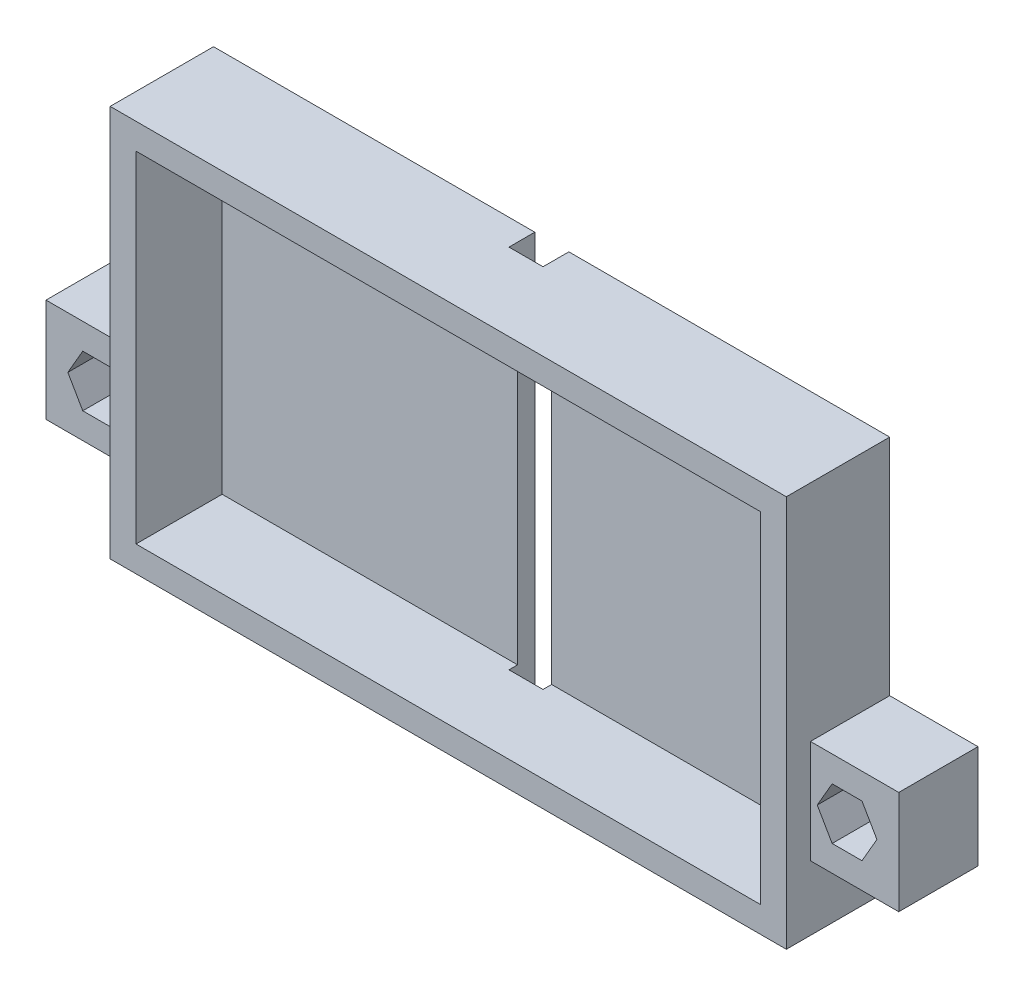
SolidWorks part; units mm, degrees
ref_plane "Plano frontal" through (0, 0, 0) normal (0, 0, 1) x (1, 0, 0)
ref_plane "Plano superior" through (0, 0, 0) normal (0, 1, 0) x (1, 0, 0)
ref_plane "Plano direito" through (0, 0, 0) normal (1, 0, 0) x (0, 0, -1)
sketch "Esboço1" plane through (0, 0, 0) normal (0, 0, 1) x (1, 0, 0)
  line L0 (0, 0) -> (0, 10.5) construction
  line L1 (0, 0) -> (-72.5, 0)
  line L2 (0, 0) -> (0, 39.5)
  line L3 (0, 39.5) -> (-72.5, 39.5)
  line L4 (-72.5, 0) -> (-72.5, 39.5)
  line L5 (-72.5, 0) -> (-72.5, 10.5) construction
  line L6 (0, 10.5) -> (7.25, 10.5) construction
  line L7 (-72.5, 10.5) -> (-79.75, 10.5) construction
  line L8 (-72.5, 39.5) -> (-75.5, 39.5) construction
  line L9 (-72.5, 39.5) -> (-72.5, 42.5) construction
  line L10 (0, 0) -> (3, 0) construction
  line L11 (0, 0) -> (0, -3) construction
  line L12 (-79.75, 10.5) -> (-79.75, 16.5) construction
  line L13 (-75.5, 42.5) -> (3, 42.5)
  line L14 (-75.5, 42.5) -> (-75.5, -3)
  line L15 (-75.5, -3) -> (3, -3)
  line L16 (3, 42.5) -> (3, -3)
  line L17 (-79.75, 10.5) -> (-85.75, 10.5) construction
  line L18 (-79.75, 10.5) -> (-79.75, 4.5) construction
  line L19 (7.25, 10.5) -> (7.25, 16.5) construction
  line L20 (7.25, 10.5) -> (13.25, 10.5) construction
  line L21 (7.25, 10.5) -> (7.25, 4.5) construction
  line L23 (-85.75, 16.5) -> (-75.5, 16.5)
  line L24 (-85.75, 16.5) -> (-85.75, 4.5)
  line L25 (-85.75, 4.5) -> (-75.5, 4.5)
  line L26 (-75.5, 16.5) -> (-75.5, 4.5)
  line L27 (13.25, 4.5) -> (3, 4.5)
  line L28 (13.25, 4.5) -> (13.25, 16.5)
  line L29 (13.25, 16.5) -> (3, 16.5)
  line L30 (3, 4.5) -> (3, 16.5)
  circle A0 centre (-79.75, 10.5) radius 1.6
  circle A1 centre (7.25, 10.5) radius 1.6
extrude "Ressalto-extrusão1" add sketch "Esboço1" along normal blind 2 contours L4 L3 L2 L1
extrude "Ressalto-extrusão2" add sketch "Esboço1<3>" along normal blind 12 contours L16 L13 L14 L15 L1 L4 L3 L2 region at (-36.25, 41.5927, 0)
sketch "Esboço1<3>" plane through (0, 0, 0) normal (0, 0, 1) x (1, 0, 0) same geometry as "Esboço1"
extrude "Ressalto-extrusão3" add sketch "Esboço1<4>" along normal blind 6 contours L24 L25 L14 L23 A0 | L28 L29 L16 L27 A1 region at (-75.6578, 10.5, 0) region at (8.125, 16.3422, 0)
sketch "Esboço1<4>" plane through (0, 0, 0) normal (0, 0, 1) x (1, 0, 0) same geometry as "Esboço1"
sketch "Esboço3" plane through (0, 0, 0) normal (0, 0, -1) x (-1, 0, 0)
  line L0 (79.75, 10.5) -> (79.75, 22.5) construction
  line L1 (79.75, 22.5) -> (68.25, 22.5) construction
  line L2 (75.5, -3) -> (-3, -3) construction
  line L3 (68.25, 22.5) -> (58.55, 22.5)
  line L4 (68.25, 22.5) -> (68.25, 25.7)
  line L5 (68.25, 25.7) -> (58.55, 25.7)
  line L6 (58.55, 22.5) -> (58.55, 25.7)
  line L7 (36.25, -3) -> (36.25, 42.5) construction
  line L8 (75.5, 42.5) -> (-3, 42.5) construction
  line L9 (-7.25, 10.5) -> (-7.25, 22.5) construction
  line L10 (-7.25, 22.5) -> (4.25, 22.5) construction
  line L11 (13.95, 22.5) -> (13.95, 25.7)
  line L12 (4.25, 25.7) -> (13.95, 25.7)
  line L13 (4.25, 22.5) -> (4.25, 25.7)
  line L14 (4.25, 22.5) -> (13.95, 22.5)
  line L15 (36.25, -3) -> (34.25, -3) construction
extrude "Ressalto-extrusão4" add sketch "Esboço3" along normal blind 3.5
sketch "Esboço5" plane through (0, 0, 0) normal (0, 0, -1) x (-1, 0, 0)
  line L0 (36.25, -3) -> (36.25, 42.5) construction
  line L1 (75.5, -3) -> (-3, -3) construction
  line L2 (75.5, 42.5) -> (-3, 42.5) construction
  line L3 (36.25, -3) -> (34.25, -3) construction
  line L5 (34.25, -3) -> (38.2025, -3)
  line L6 (34.25, -3) -> (34.25, 42.5)
  line L7 (34.25, 42.5) -> (38.2025, 42.5)
  line L8 (38.2025, -3) -> (38.2025, 42.5)
extrude "Corte-extrusão4" cut sketch "Esboço5" against normal blind 3
sketch "Esboço7" plane through (-58.55, 0, 0) normal (1, 0, 0) x (0, 0, -1)
  line L0 (3.5, 25.7) -> (3.5, 26.2)
  line L1 (3.5, 25.7) -> (4.5, 25.7) construction
  line L2 (3.5, 26.2) -> (4.5, 25.7)
  line L3 (4.5, 25.7) -> (3.5, 22.5)
  line L10 (3.5, 22.5) -> (3.5, 25.7)
extrude "Ressalto-extrusão5" add sketch "Esboço7" against normal up to surface (9.7 mm away) up to face at (-68.25, 24.1, -1.75)
sketch "Esboço8" plane through (-4.25, 0, 0) normal (1, 0, 0) x (0, 0, -1)
  line L0 (3.5, 25.7) -> (3.5, 26.2)
  line L1 (3.5, 25.7) -> (4.5, 25.7) construction
  line L2 (3.5, 26.2) -> (4.5, 25.7)
  line L3 (4.5, 25.7) -> (3.5, 22.5)
  line L15 (3.5, 22.5) -> (3.5, 25.7)
extrude "Ressalto-extrusão6" add sketch "Esboço8" against normal up to surface (9.7 mm away) up to face at (-13.95, 24.1, -1.75)
ref_plane "Plano1" through (0, 0, -10) normal (0, 0, -1) x (-1, 0, 0)
sketch "Esboço9" plane through (0, 0, -10) normal (0, 0, -1) x (-1, 0, 0)
  line L1 (-2.547, 31.4646) -> (77.239, 31.4646)
  line L2 (-2.547, 31.4646) -> (-2.547, 10.2704)
  line L3 (-2.547, 10.2704) -> (77.239, 10.2704)
  line L4 (77.239, 31.4646) -> (77.239, 10.2704)
extrude "Corte-extrusão5" cut sketch "Esboço9" against normal up to vertex (10 mm away) up to point (3, 42.5, 0)
sketch "Esboço10" plane through (0, 0, 6) normal (0, 0, 1) x (1, 0, 0)
  line L0 (-85.75, 16.5) -> (-85.75, 4.5) construction
  line L1 (-85.75, 4.5) -> (-75.5, 4.5) construction
  line L2 (-75.5, 4.5) -> (-75.5, 16.5) construction
  line L3 (-75.5, 16.5) -> (-85.75, 16.5) construction
  line L4 (13.25, 4.5) -> (13.25, 16.5) construction
  line L5 (13.25, 16.5) -> (3, 16.5) construction
  line L6 (3, 16.5) -> (3, 4.5) construction
  line L7 (3, 4.5) -> (13.25, 4.5) construction
  line L8 (-85.75, 16.5) -> (-85.75, 4.5)
  line L9 (-85.75, 4.5) -> (-75.5, 4.5)
  line L10 (-75.5, 4.5) -> (-75.5, 16.5)
  line L11 (-75.5, 16.5) -> (-85.75, 16.5)
  line L12 (13.25, 4.5) -> (13.25, 16.5)
  line L13 (13.25, 16.5) -> (3, 16.5)
  line L14 (3, 16.5) -> (3, 4.5)
  line L15 (3, 4.5) -> (13.25, 4.5)
sketch "Esboço11" plane through (0, 0, 6) normal (0, 0, 1) x (1, 0, 0)
  line L0 (13.25, 4.5) -> (13.25, 16.5) construction
  line L1 (13.25, 16.5) -> (3, 16.5) construction
  line L2 (3, 16.5) -> (3, 4.5) construction
  line L3 (3, 4.5) -> (13.25, 4.5) construction
  line L4 (-85.75, 16.5) -> (-85.75, 4.5) construction
  line L5 (-85.75, 4.5) -> (-75.5, 4.5) construction
  line L6 (-75.5, 4.5) -> (-75.5, 16.5) construction
  line L7 (-75.5, 16.5) -> (-85.75, 16.5) construction
  line L8 (13.25, 4.5) -> (13.25, 16.5)
  line L9 (13.25, 16.5) -> (3, 16.5)
  line L10 (3, 16.5) -> (3, 4.5)
  line L11 (3, 4.5) -> (13.25, 4.5)
  line L12 (-85.75, 16.5) -> (-85.75, 4.5)
  line L13 (-85.75, 4.5) -> (-75.5, 4.5)
  line L14 (-75.5, 4.5) -> (-75.5, 16.5)
  line L15 (-75.5, 16.5) -> (-85.75, 16.5)
extrude "Ressalto-extrusão8" add sketch "Esboço11" along normal blind 1.2
sketch "Esboço12" plane through (0, 0, -10) normal (0, 0, -1) x (-1, 0, 0)
  circle A0 centre (-7.25, 10.5) radius 1.6 construction
  circle A1 centre (79.75, 10.5) radius 1.6 construction
  circle A2 centre (-7.25, 10.5) radius 1.6
  circle A3 centre (79.75, 10.5) radius 1.6
extrude "Corte-extrusão6" cut sketch "Esboço12" against normal through all
sketch "Esboço13" plane through (0, 0, 7.2) normal (0, 0, 1) x (1, 0, 0)
  line L1 (-83.2141, 10.5) -> (-81.4821, 7.5)
  line L2 (-81.4821, 7.5) -> (-78.0179, 7.5)
  line L3 (-78.0179, 7.5) -> (-76.2859, 10.5)
  line L4 (-76.2859, 10.5) -> (-78.0179, 13.5)
  line L5 (-78.0179, 13.5) -> (-81.4821, 13.5)
  line L6 (-81.4821, 13.5) -> (-83.2141, 10.5)
  line L7 (10.7141, 10.5) -> (8.9821, 13.5)
  line L8 (8.9821, 13.5) -> (5.5179, 13.5)
  line L9 (5.5179, 13.5) -> (3.7859, 10.5)
  line L10 (3.7859, 10.5) -> (5.5179, 7.5)
  line L11 (5.5179, 7.5) -> (8.9821, 7.5)
  line L12 (8.9821, 7.5) -> (10.7141, 10.5)
  circle A0 centre (-79.75, 10.5) radius 1.6 construction
  circle A1 centre (7.25, 10.5) radius 1.6 construction
  circle A2 centre (-79.75, 10.5) radius 1.6
  circle A3 centre (7.25, 10.5) radius 1.6
  circle A4 centre (-79.75, 10.5) radius 3 construction
  circle A5 centre (7.25, 10.5) radius 3 construction
extrude "Corte-extrusão7" cut sketch "Esboço13" against normal blind 3.75
sketch "Esboço14" plane through (0, 0, 7.2) normal (0, 0, 1) x (1, 0, 0)
  line L0 (3, 4.5) -> (13.25, 4.5) construction
  line L1 (13.25, 4.5) -> (13.25, 16.5) construction
  line L2 (13.25, 16.5) -> (3, 16.5) construction
  line L3 (3, 16.5) -> (3, 4.5) construction
  line L4 (-75.5, 16.5) -> (-85.75, 16.5) construction
  line L5 (-85.75, 16.5) -> (-85.75, 4.5) construction
  line L6 (-85.75, 4.5) -> (-75.5, 4.5) construction
  line L7 (-75.5, 4.5) -> (-75.5, 16.5) construction
  line L8 (3, 4.5) -> (13.25, 4.5)
  line L9 (13.25, 4.5) -> (13.25, 16.5)
  line L10 (13.25, 16.5) -> (3, 16.5)
  line L11 (3, 16.5) -> (3, 4.5)
  line L12 (-75.5, 16.5) -> (-85.75, 16.5)
  line L13 (-85.75, 16.5) -> (-85.75, 4.5)
  line L14 (-85.75, 4.5) -> (-75.5, 4.5)
  line L15 (-75.5, 4.5) -> (-75.5, 16.5)
  line L16 (8.9821, 7.5) -> (10.7141, 10.5) construction
  line L17 (10.7141, 10.5) -> (8.9821, 13.5) construction
  line L18 (8.9821, 13.5) -> (5.5179, 13.5) construction
  line L19 (5.5179, 13.5) -> (3.7859, 10.5) construction
  line L20 (3.7859, 10.5) -> (5.5179, 7.5) construction
  line L21 (5.5179, 7.5) -> (8.9821, 7.5) construction
  line L22 (-81.4821, 13.5) -> (-83.2141, 10.5) construction
  line L23 (-83.2141, 10.5) -> (-81.4821, 7.5) construction
  line L24 (-81.4821, 7.5) -> (-78.0179, 7.5) construction
  line L25 (-78.0179, 7.5) -> (-76.2859, 10.5) construction
  line L26 (-76.2859, 10.5) -> (-78.0179, 13.5) construction
  line L27 (-78.0179, 13.5) -> (-81.4821, 13.5) construction
  line L28 (8.9821, 7.5) -> (10.7141, 10.5)
  line L29 (10.7141, 10.5) -> (8.9821, 13.5)
  line L30 (8.9821, 13.5) -> (5.5179, 13.5)
  line L31 (5.5179, 13.5) -> (3.7859, 10.5)
  line L32 (3.7859, 10.5) -> (5.5179, 7.5)
  line L33 (5.5179, 7.5) -> (8.9821, 7.5)
  line L34 (-81.4821, 13.5) -> (-83.2141, 10.5)
  line L35 (-83.2141, 10.5) -> (-81.4821, 7.5)
  line L36 (-81.4821, 7.5) -> (-78.0179, 7.5)
  line L37 (-78.0179, 7.5) -> (-76.2859, 10.5)
  line L38 (-76.2859, 10.5) -> (-78.0179, 13.5)
  line L39 (-78.0179, 13.5) -> (-81.4821, 13.5)
extrude "Ressalto-extrusão10" add sketch "Esboço14" along normal blind 2
